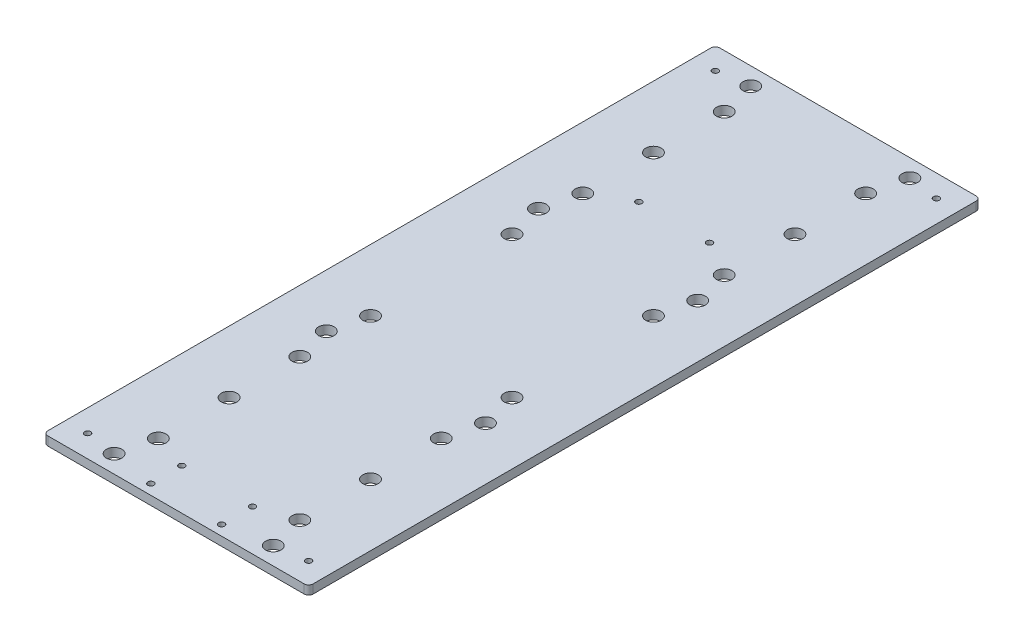
SolidWorks part; units mm, degrees
material "Plain Carbon Steel"
ref_plane "Front Plane" through (0, 0, 0) normal (0, 0, 1) x (1, 0, 0)
ref_plane "Top Plane" through (0, 0, 0) normal (0, 1, 0) x (1, 0, 0)
ref_plane "Right Plane" through (0, 0, 0) normal (1, 0, 0) x (0, 0, -1)
sketch "Sketch1" plane through (0, 29.1433, 0) normal (0, -1, 0) x (1, 0, 0)
  line L0 (-328.3006, -181.5669) -> (-282.3006, -181.5669) construction
  line L1 (-35.3006, 578.4331) -> (-325.3006, 578.4331)
  line L2 (-30.3006, 573.4331) -> (-30.3006, -176.5669)
  line L3 (-35.3006, -181.5669) -> (-325.3006, -181.5669)
  line L4 (-330.3006, 573.4331) -> (-330.3006, -176.5669)
  line L6 (-330.3006, 578.4331) -> (-330.3006, -181.5669) construction
  arc A0 (-325.3006, -181.5669) -> (-330.3006, -176.5669) centre (-325.3006, -176.5669) cw
  arc A1 (-30.3006, -176.5669) -> (-35.3006, -181.5669) centre (-35.3006, -176.5669) cw
  arc A2 (-35.3006, 578.4331) -> (-30.3006, 573.4331) centre (-35.3006, 573.4331) cw
  arc A3 (-325.3006, 578.4331) -> (-330.3006, 573.4331) centre (-325.3006, 573.4331) ccw
  point P11 (-30.3006, 578.4331)
  dimension "D1" = 5
extrude "Boss-Extrude1" add sketch "Sketch1" along normal blind 10
sketch "Centerlines" plane through (0, 29.1433, 0) normal (0, 1, 0) x (1, 0, 0)
  line L0 (-180.3006, 181.5669) -> (-180.3006, -578.4331) construction
  line L1 (-325.3006, 181.5669) -> (-35.3006, 181.5669) construction
  line L2 (-35.3006, -578.4331) -> (-325.3006, -578.4331) construction
  line L3 (-30.3006, -198.4331) -> (-330.3006, -198.4331) construction
  line L4 (-30.3006, 176.5669) -> (-30.3006, -573.4331) construction
  line L5 (-330.3006, -573.4331) -> (-330.3006, 176.5669) construction
  line L6 (-270.3006, 181.5669) -> (-270.3006, -78.4331) construction
  line L7 (-270.3006, -78.4331) -> (-270.3006, -198.4331) construction
  line L8 (-270.3006, -198.4331) -> (-270.3006, -318.4331) construction
  line L9 (-270.3006, -318.4331) -> (-270.3006, -578.4331) construction
  line L10 (-90.3006, -318.4331) -> (-90.3006, -578.4331) construction
  line L11 (-90.3006, -198.4331) -> (-90.3006, -318.4331) construction
  line L12 (-90.3006, -78.4331) -> (-90.3006, -198.4331) construction
  line L13 (-90.3006, 181.5669) -> (-90.3006, -78.4331) construction
  line L14 (-260.3006, 181.5669) -> (-260.3006, -198.4331) construction
  line L15 (-325.3006, 181.5669) -> (-35.3006, 181.5669) construction
  line L16 (-260.3006, -198.4331) -> (-260.3006, -578.4331) construction
  line L17 (-35.3006, -578.4331) -> (-325.3006, -578.4331) construction
  line L18 (-100.3006, -198.4331) -> (-100.3006, -578.4331) construction
  line L19 (-100.3006, 181.5669) -> (-100.3006, -198.4331) construction
  line L20 (-100.3006, -38.4331) -> (-260.3006, -38.4331) construction
  point P12 (-180.3006, -198.4331)
  point P23 (-270.3006, -558.4331)
  point P24 (-90.3006, -558.4331)
  point P25 (-270.3006, 161.5669)
  point P26 (-90.3006, 161.5669)
  point P37 (-100.3006, 41.5669)
  point P38 (-100.3006, 121.5669)
  point P41 (-100.3006, -118.4331)
  point P42 (-100.3006, -518.4331)
  point P43 (-100.3006, -438.4331)
  point P44 (-100.3006, -358.4331)
  point P45 (-100.3006, -278.4331)
  point P46 (-260.3006, -518.4331)
  point P47 (-260.3006, -438.4331)
  point P48 (-260.3006, -358.4331)
  point P49 (-260.3006, -278.4331)
  point P50 (-260.3006, -118.4331)
  point P51 (-260.3006, 41.5669)
  point P52 (-260.3006, 121.5669)
  dimension "D1" = 180
  dimension "D2" = 240
  dimension "D3" = 240
  dimension "D4" = 160
  dimension "D5" = 80
  dimension "D6" = 40
  dimension "D7" = 80
hole_wizard "M8 Tapped Hole" positions "Sketch2" profile "Sketch3" tap size "M8" standard "ISO" end condition through all
sketch "Sketch2" plane through (-171.5962, 38.1433, 73.097) normal (0, 1, 0) x (1, 0, 0)
  point P0 (-48.7044, -458.8361)
  point P3 (-48.7044, -493.8361)
  point P6 (31.2956, -493.8361)
  point P9 (31.2956, -458.8361)
  point P12 (31.2956, 58.0784)
  point P15 (-48.7044, 58.0784)
sketch "Sketch3" plane through (-220.3006, 38.1433, 531.9331) normal (1, 0, 0) x (0, 0, 1)
  line L0 (0, 0) -> (0, 19)
  line L1 (0, 19) -> (3.4, 19)
  line L2 (3.4, 19) -> (3.4, 0)
  line L3 (3.4, 0) -> (0, 0)
  line L4 (0, -6.35) -> (0, 107.95) construction
  dimension "Thread Major Dia." = 6.8
  dimension "Thru Tap Drill Depth" = 19
hole_wizard "M16 Clearance Hole1" positions "Sketch4" profile "Sketch5" hole size "M16" standard "ISO" end condition through all
sketch "Sketch4" plane through (0, 29.1433, 0) normal (0, 1, 0) x (1, 0, 0)
  point P0 (-270.3006, -78.4331)
  point P3 (-90.3006, -78.4331)
  point P6 (-90.3006, -318.4331)
  point P9 (-270.3006, -318.4331)
  point P12 (-270.3006, 161.5669)
  point P15 (-90.3006, 161.5669)
  point P18 (-270.3006, -558.4331)
  point P21 (-90.3006, -558.4331)
  point P24 (-260.3006, 121.5669)
  point P27 (-260.3006, 41.5669)
  point P30 (-260.3006, -118.4331)
  point P33 (-260.3006, -278.4331)
  point P36 (-260.3006, -358.4331)
  point P39 (-260.3006, -438.4331)
  point P42 (-260.3006, -518.4331)
  point P45 (-100.3006, -518.4331)
  point P48 (-100.3006, -438.4331)
  point P51 (-100.3006, -358.4331)
  point P54 (-100.3006, -278.4331)
  point P57 (-100.3006, -118.4331)
  point P60 (-100.3006, 41.5669)
  point P63 (-100.3006, -38.4331)
  point P66 (-260.3006, -38.4331)
  point P69 (-100.3006, 121.5669)
sketch "Sketch5" plane through (-270.3006, 29.1433, 78.4331) normal (1, 0, 0) x (0, 0, 1)
  line L0 (0, 0) -> (0, 10)
  line L1 (0, 10) -> (8.75, 10)
  line L2 (8.75, 10) -> (8.75, 0)
  line L3 (8.75, 0) -> (0, 0)
  line L4 (0, -6.35) -> (0, 107.95) construction
  dimension "Thru Hole Dia." = 17.5
  dimension "Thru Hole Depth" = 10
hole_wizard "M8 Tapped Hole2" positions "Sketch8" profile "Sketch9" tap size "M8" standard "ISO" end condition through all
sketch "Sketch8" plane through (-180.6417, 19.1433, 85.5993) normal (0, -1, 0) x (-1, 0, 0)
  point P0 (124.6589, -467.8339)
  point P3 (-125.3411, -467.8339)
  point P6 (124.6589, 242.1661)
  point P9 (-125.3411, 242.1661)
sketch "Sketch9" plane through (-305.3006, 19.1433, 553.4331) normal (1, 0, 0) x (0, 0, -1)
  line L0 (0, 0) -> (0, 10)
  line L1 (0, 10) -> (3.4, 10)
  line L2 (3.4, 10) -> (3.4, 0)
  line L3 (3.4, 0) -> (0, 0)
  line L4 (0, -6.35) -> (0, 107.95) construction
  dimension "Thread Major Dia." = 6.8
  dimension "Thru Tap Drill Depth" = 10
